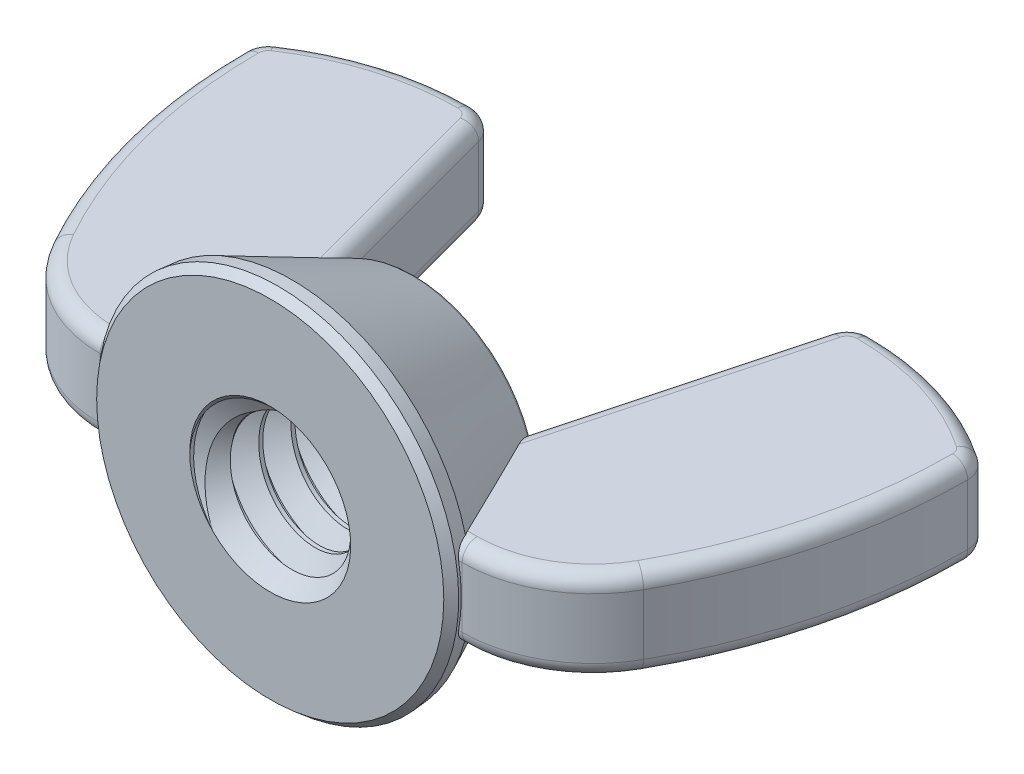
SolidWorks part; units mm, degrees
ref_plane "Front Plane" through (0, 0, 0) normal (0, 0, 1) x (1, 0, 0)
ref_plane "Top Plane" through (0, 0, 0) normal (0, 1, 0) x (1, 0, 0)
ref_plane "Right Plane" through (0, 0, 0) normal (1, 0, 0) x (0, 0, -1)
sketch "Sketch1" plane through (0, 0, 0) normal (0, 0, 1) x (1, 0, 0)
  circle A0 centre (0, 0) radius 3.175
  circle A1 centre (0, 0) radius 7.1438
  dimension "D1" = 14.2875
  dimension "thread dia" = 6.35
sketch "Sketch2" plane through (0, 0, 0) normal (0, 1, 0) x (1, 0, 0)
  line L0 (0, 0) -> (0, 15.875) construction
  line L1 (-3.175, 0) -> (3.175, 0) construction
  line L2 (-14.2875, 15.875) -> (14.2875, 15.875) construction
  line L3 (14.2875, 15.875) -> (14.2875, 0) construction
  line L4 (-14.2875, 15.875) -> (-14.2875, 0) construction
  line L5 (-14.2875, 0) -> (14.2875, 0) construction
  line L6 (-4.8774, 5.715) -> (4.8774, 5.715) construction
  line L7 (0, 0) -> (0, 5.715) construction
  line L8 (-4.3144, 0.8572) -> (7.1438, 0.8572) construction
  line L9 (7.1438, 0) -> (7.1438, 5.715) construction
  line L10 (4.3897, 5.715) -> (7.1809, 16.132)
  line L12 (4.8774, 5.715) -> (4.8774, 0.4286) construction
  line L13 (-7.1438, 0) -> (7.1438, 0) construction
  line L14 (7.1438, 0.8572) -> (4.8774, 5.715) construction
  line L15 (7.1809, 16.132) -> (14.5708, 13.8727)
  line L16 (14.5708, 13.8727) -> (9.8978, 0.4286)
  line L17 (7.1438, 0.4286) -> (9.8978, 0.4286)
  line L19 (4.3897, 0.4286) -> (7.1438, 0.4286)
  line L20 (-4.3897, 5.715) -> (4.3897, 5.715) construction
  line L21 (4.3897, 5.715) -> (4.3897, 0.4286)
  circle A3 centre (13.2953, 13.2252) radius 0.9922 construction
  circle A4 centre (7.8734, 14.8828) radius 0.9922 construction
  dimension "D6" = 1.9844
  dimension "D7" = 15
  dimension "D1" = 0.8572
  dimension "A" = 28.575
  dimension "B" = 15.875
  dimension "D2" = 5.715
  dimension "D3" = 25.011
  dimension "D4" = 9.7549
  dimension "D5" = 0.4286
  dimension "D8" = 17
  dimension "D9" = 8.7794
sketch "Sketch13" plane through (0, 0, 0) normal (0, 1, 0) x (1, 0, 0)
  line L1 (4.3897, 5.715) -> (4.3897, 0.4286) construction
  line L2 (4.3897, 5.715) -> (7.1809, 16.132) construction
  line L3 (-14.2875, 15.875) -> (14.2875, 15.875) construction
  line L4 (14.2875, 15.875) -> (14.2875, 0) construction
  line L5 (7.1438, 0.4286) -> (9.8978, 0.4286) construction
  line L6 (4.3897, 0.4286) -> (7.1438, 0.4286) construction
  line L7 (0, 0) -> (0, 5.715) construction
  line L8 (-3.175, 0) -> (3.175, 0) construction
  line L9 (0, 0) -> (0, 15.875) construction
  line L10 (-4.8774, 5.715) -> (4.8774, 5.715) construction
  line L11 (4.3897, 0.4286) -> (7.1438, 0.4286)
  line L12 (4.3897, 5.715) -> (4.3897, 0.4286)
  line L13 (4.3897, 5.715) -> (6.915, 15.1396)
  circle A0 centre (13.2953, 13.2252) radius 0.9922 construction
  circle A1 centre (7.8734, 14.8828) radius 0.9922 construction
  arc A5 (14.2875, 13.2252) -> (13.8501, 14.0477) centre (13.2953, 13.2252) ccw
  arc A6 (7.8734, 15.875) -> (6.915, 15.1396) centre (7.8734, 14.8828) ccw
  arc A7 (11.6501, 3.076) -> (14.2875, 13.2252) centre (-6.5592, 13.2252) ccw
  arc A8 (13.8501, 14.0477) -> (7.8734, 15.875) centre (7.8734, 5.1868) ccw
  arc A10 (7.1438, 0.4286) -> (11.6501, 3.076) centre (7.1437, 5.5877) ccw
extrude "Extrude2" add sketch "Sketch13" along normal mid plane 3.5719
sketch "Sketch3" plane through (0, 0, 0) normal (0, 0, 1) x (1, 0, 0)
  circle A0 centre (0, 0) radius 7.1438 construction
  circle A1 centre (0, 0) radius 7.1438
extrude "Extrude1" add sketch "Sketch3" against normal up to vertex (0.8572 mm away) draft 5 separate body up to point (7.1438, 0, -0.8572)
sketch "Sketch15" plane through (0, 0, -0.8572) normal (0, 0, -1) x (-1, 0, 0)
  circle A1 centre (0, 0) radius 7.0688
  circle A2 centre (0, 0) radius 7.0688
  dimension "D1" = 0
extrude "Extrude3" add sketch "Sketch15" along normal up to vertex (4.8578 mm away) draft 25.011 up to point (0, 0, -5.715)
fillet "Fillet3" radius 0.254 1 edges at (-4.8024, 0, -5.715)
sketch "Sketch12" plane through (0, 0, -5.715) normal (0, 0, -1) x (-1, 0, 0)
  circle A1 centre (0, 0) radius 7.0688
  circle A2 centre (0, 0) radius 7.0688 construction
  dimension "D1" = 14.1375
sketch "Sketch4" plane through (0, 0, 0) normal (0, 0, 1) x (1, 0, 0)
  circle A0 centre (0, 0) radius 3.175 construction
  circle A1 centre (0, 0) radius 3.175
extrude "Cut-Extrude1" cut sketch "Sketch4" against normal through all
sketch "Sketch5" plane through (0, 0, 0) normal (0, 0, 1) x (1, 0, 0)
  circle A0 centre (0, 0) radius 3.175 construction
  circle A1 centre (0, 0) radius 3.175
curve "Helix/Spiral1" pitch 1.27 height 8.89 turns 7 parameters "pitch"=1.27
sketch "Sketch6" plane through (0, 0, 0) normal (0, 1, 0) x (1, 0, 0)
  line L0 (-3.175, -1.1112) -> (-2.3501, -0.635)
  line L1 (-2.3501, -0.635) -> (-2.3501, -0.4762)
  line L2 (-2.3501, -0.4762) -> (-3.175, 0)
  line L3 (-3.175, -1.1112) -> (-3.175, 0)
  line L4 (-3.175, -0.5556) -> (-2.3501, -0.5556) construction
  line L5 (-2.7626, -0.8731) -> (-2.7626, -0.2381) construction
  line L6 (-3.175, 0) -> (3.175, 0) construction
  dimension "D1" = 60
  dimension "D2" = 0.1588
  dimension "D3" = 0.635
sweep "Sweep1" add profiles "Sketch6" path "Helix/Spiral1"
sketch "Sketch7" plane through (0, 0, 0) normal (0, 0, 1) x (1, 0, 0)
  circle A1 centre (0, 0) radius 7.1438
  circle A2 centre (0, 0) radius 7.1438
  dimension "D1" = 0
extrude "Cut-Extrude2" cut sketch "Sketch7" along normal through all
ref_plane "Plane1" through (0, 0, -5.715) normal (0, 0, 1) x (1, 0, 0)
sketch "Sketch8" plane through (0, 0, -5.715) normal (0, 0, 1) x (1, 0, 0)
  circle A0 centre (0, 0) radius 7.0688 construction
  circle A2 centre (0, 0) radius 7.0688
extrude "Cut-Extrude3" cut sketch "Sketch8" against normal through all
sketch "Sketch9" plane through (0, 0, 0) normal (0, 0, 1) x (1, 0, 0)
  circle A1 centre (0, 0) radius 3.175
  circle A2 centre (0, 0) radius 3.175
  dimension "D1" = 0
extrude "Cut-Extrude4" cut sketch "Sketch9" against normal through all draft 45
sketch "Sketch11" plane through (0, 0, -5.715) normal (0, 0, 1) x (1, 0, 0)
  circle A0 centre (0, 0) radius 3.175 construction
  circle A1 centre (0, 0) radius 3.1242
  circle A2 centre (0, 0) radius 3.175 construction
  dimension "D1" = 0.0508
extrude "Cut-Extrude5" cut sketch "Sketch11" along normal through all draft 45
chamfer "Chamfer1" distance 0.3215 angle 45 1 edges at (7.1438, 0, 0)
fillet "Fillet4" radius 0.5953 14 edges at (5.7667, 1.7859, -0.4286) (9.757, 1.7859, -1.1394) (7.2694, 1.7859, -15.67) (10.9983, 1.7859, -15.408) (14.1714, 1.7859, -13.691) (5.7667, -1.7859, -0.4286) (9.757, -1.7859, -1.1394) (7.2694, -1.7859, -15.67) (10.9983, -1.7859, -15.408) (14.1714, -1.7859, -13.691) (13.6174, 1.7859, -7.982) (13.6174, -1.7859, -7.982) (5.6524, 1.7859, -10.4273) (5.6524, -1.7859, -10.4273)
mirror "Mirror6" about plane through (0, 0, 0) normal (1, 0, 0) of bodies 108 113
combine bodies "Combine2" operation type add bodies to combine 116 108 107
equation "\"D1@Sketch1\" = \"thread dia@Sketch1\"*1.725"
equation "\"D2@Sketch2\" = \"B@Sketch2\"*.36"
equation "\"D3@Helix/Spiral1\" = \"D2@Sketch2\"+.125"
equation "\"D2@Sketch6\" = \"pitch@Helix/Spiral1\"*.125"
equation "\"D3@Sketch6\" = \"pitch@Helix/Spiral1\"*.5"
equation "\"D4@Sketch2\" = \"D1@Sketch12\"*.69"
equation "\"D1@Extrude2\" = \"D1@Sketch1\"*.25"
equation "\"D1@Sketch2\" = \"D2@Sketch2\"*.150"
equation "\"D5@Sketch2\" = \"D1@Sketch2\"/2"
equation "\"D3@Extrude3\" = \"D3@Sketch2\""
equation "\"D1@Chamfer1\" = \"D5@Sketch2\"*.75"
equation "\"D9@Sketch2\" = \"D4@Sketch2\"*.9"
equation "\"D6@Sketch2\" = \"D1@Extrude2\"/1.8"
equation "\"D1@Fillet4\" = \"D1@Extrude2\"/6"
